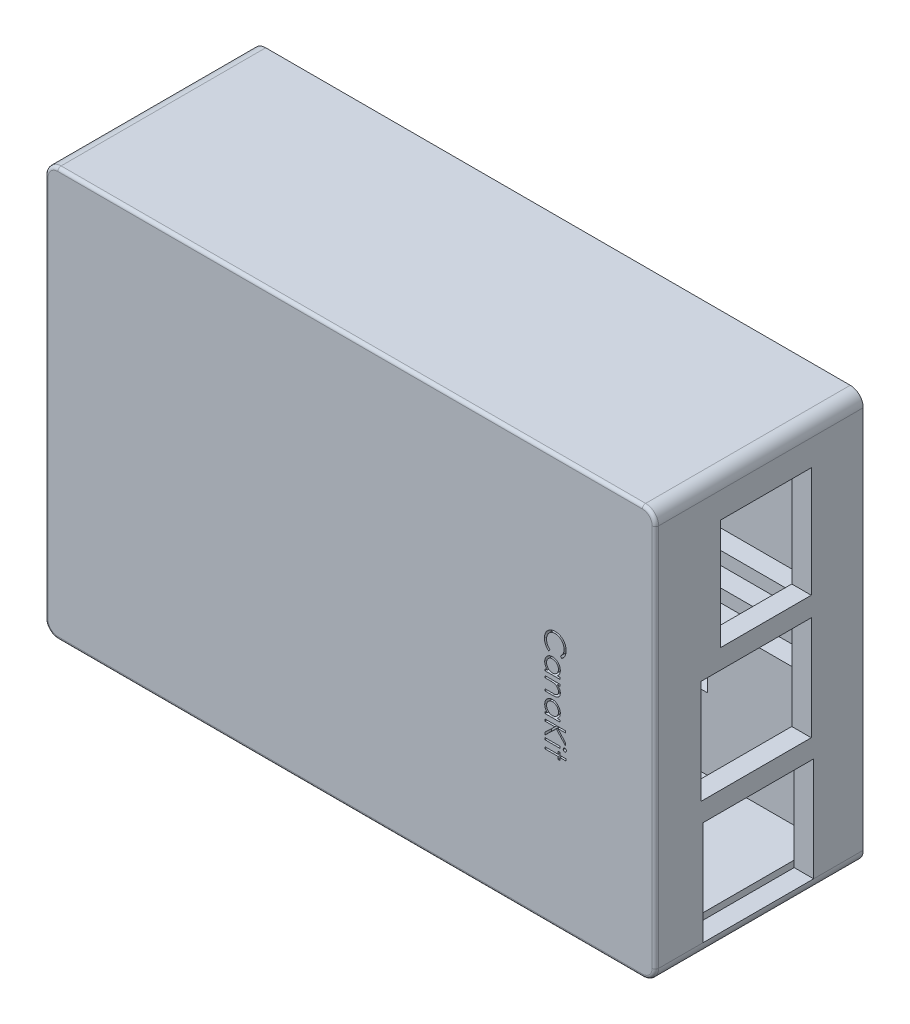
SolidWorks part; units mm, degrees
ref_plane "Front Plane" through (0, 0, 0) normal (0, 0, 1) x (1, 0, 0)
ref_plane "Top Plane" through (0, 0, 0) normal (0, 1, 0) x (1, 0, 0)
ref_plane "Right Plane" through (0, 0, 0) normal (1, 0, 0) x (0, 0, -1)
sketch "Sketch1" plane through (0, 0, 0) normal (0, 0, 1) x (1, 0, 0)
  line L1 (0, 0) -> (94, 0)
  line L2 (0, 0) -> (0, 63)
  line L3 (0, 63) -> (94, 63)
  line L4 (94, 0) -> (94, 63)
  dimension "D1" = 94
  dimension "D2" = 63
extrude "Boss-Extrude1" add sketch "Sketch1" along normal blind 32
shell "Shell1" thickness 3
sketch "Sketch2" plane through (0, 0, 0) normal (-1, 0, 0) x (0, 0, 1)
  line L0 (0, 63) -> (0, 0) construction
  line L1 (8, 40) -> (0, 40)
  line L2 (8, 40) -> (8, 23)
  line L3 (8, 23) -> (0, 23)
  line L4 (0, 40) -> (0, 23)
  line L5 (32, 63) -> (0, 63) construction
  dimension "D1" = 17
  dimension "D2" = 8
  dimension "D3" = 0
  dimension "D4" = 23
extrude "Cut-Extrude1" cut sketch "Sketch2" against normal blind 3
sketch "Sketch3" plane through (94, 0, 0) normal (1, 0, 0) x (0, 0, -1)
  line L0 (-32, 63) -> (0, 63) construction
  line L1 (-22, 40) -> (-8, 40)
  line L2 (-22, 40) -> (-22, 57)
  line L3 (-22, 57) -> (-8, 57)
  line L4 (-8, 40) -> (-8, 57)
  line L5 (0, 0) -> (0, 63) construction
  dimension "D1" = 17
  dimension "D2" = 14
  dimension "D3" = 6
  dimension "D4" = 8
extrude "Cut-Extrude2" cut sketch "Sketch3" against normal blind 3
sketch "Sketch4" plane through (94, 0, 0) normal (1, 0, 0) x (0, 0, -1)
  line L0 (-22, 40) -> (-8, 40) construction
  line L1 (-25, 21) -> (-8, 21)
  line L2 (-25, 21) -> (-25, 37)
  line L3 (-25, 37) -> (-8, 37)
  line L4 (-8, 21) -> (-8, 37)
  line L5 (0, 0) -> (0, 63) construction
  dimension "D1" = 16
  dimension "D2" = 17
  dimension "D3" = 3
  dimension "D4" = 8
extrude "Cut-Extrude4" cut sketch "Sketch4" against normal blind 3
sketch "Sketch5" plane through (94, 0, 0) normal (1, 0, 0) x (0, 0, -1)
  line L0 (-25, 21) -> (-8, 21) construction
  line L1 (-24.6328, 2) -> (-7.6328, 2)
  line L2 (-24.6328, 2) -> (-24.6328, 18)
  line L3 (-24.6328, 18) -> (-7.6328, 18)
  line L4 (-7.6328, 2) -> (-7.6328, 18)
  dimension "D1" = 17
  dimension "D2" = 16
  dimension "D3" = 3
extrude "Cut-Extrude5" cut sketch "Sketch5" against normal blind 3
sketch "Sketch6" plane through (0, 0, 0) normal (0, -1, 0) x (-1, 0, 0)
  line L0 (-94, -32) -> (-94, 0) construction
  line L1 (0, 0) -> (-94, 0) construction
  circle A0 centre (-59, -11) radius 1.75
  dimension "D1" = 3.5
  dimension "D2" = 35
  dimension "D3" = 11
extrude "Cut-Extrude6" cut sketch "Sketch6" against normal blind 3
sketch "Sketch7" plane through (0, 0, 0) normal (0, -1, 0) x (-1, 0, 0)
  line L0 (0, 0) -> (-94, 0) construction
  line L1 (-43, -11) -> (-52, -11)
  line L2 (-43, -11) -> (-43, -8)
  line L3 (-43, -8) -> (-52, -8)
  line L4 (-52, -11) -> (-52, -8)
  line L5 (-28, -11) -> (-37, -11)
  line L6 (-28, -11) -> (-28, -8)
  line L7 (-28, -8) -> (-37, -8)
  line L8 (-37, -11) -> (-37, -8)
  line L9 (-14, -10.5) -> (-22, -10.5)
  line L10 (-14, -10.5) -> (-14, -8)
  line L11 (-14, -8) -> (-22, -8)
  line L12 (-22, -10.5) -> (-22, -8)
  circle A0 centre (-59, -11) radius 1.75 construction
  dimension "D1" = 9
  dimension "D2" = 3
  dimension "D3" = 8
  dimension "D4" = 7
  dimension "D5" = 9
  dimension "D6" = 3
  dimension "D7" = 8
  dimension "D8" = 6
  dimension "D9" = 8
  dimension "D10" = 2.5
  dimension "D11" = 6
  dimension "D12" = 8
extrude "Cut-Extrude7" cut sketch "Sketch7" against normal blind 3
sketch "Sketch9" plane through (0, 0, 32) normal (0, 0, 1) x (1, 0, 0)
  line L0 (77, 60.4844) -> (77, 1.6207) construction
  line L1 (94, 0) -> (94, 63) construction
  text T0 "CanaKit"
  dimension "D1" = 17
extrude "Cut-Extrude8" cut sketch "Sketch9" against normal blind 1
sketch "Sketch11" plane through (0, 0, 0) normal (0, -1, 0) x (1, 0, 0)
  line L0 (-5.7016, 1.5) -> (107.7038, 1.5) construction
  line L1 (0, 0) -> (94, 0) construction
  text T0 "             PWR       HDMI     HDMI    A/V" font "Century Gothic" height in points 10
  dimension "D1" = 1.5
extrude "Cut-Extrude9" cut sketch "Sketch11" against normal blind 1
sketch "Sketch14" plane through (0, 0, 0) normal (0, 0, -1) x (-1, 0, 0)
  line L0 (-94, 63) -> (0, 63) construction
  line L1 (-70, 52) -> (-20, 52)
  line L2 (-70, 52) -> (-70, 49)
  line L3 (-70, 49) -> (-20, 49)
  line L4 (-20, 52) -> (-20, 49)
  line L5 (-94, 0) -> (-94, 63) construction
  line L7 (-73, 47) -> (-23, 47)
  line L8 (-73, 47) -> (-73, 44)
  line L9 (-73, 44) -> (-23, 44)
  line L10 (-23, 47) -> (-23, 44)
  line L11 (-75, 42) -> (-15, 42)
  line L12 (-75, 42) -> (-75, 39)
  line L13 (-75, 39) -> (-15, 39)
  line L14 (-15, 42) -> (-15, 39)
  line L15 (-89, 37) -> (-13, 37)
  line L16 (-89, 37) -> (-89, 34)
  line L17 (-89, 34) -> (-13, 34)
  line L18 (-13, 37) -> (-13, 34)
  line L19 (-86, 32) -> (-10, 32)
  line L20 (-86, 32) -> (-86, 29)
  line L21 (-86, 29) -> (-10, 29)
  line L22 (-10, 32) -> (-10, 29)
  line L23 (-89, 24) -> (-13, 24)
  line L24 (-89, 24) -> (-89, 27)
  line L25 (-89, 27) -> (-13, 27)
  line L26 (-13, 24) -> (-13, 27)
  line L27 (-75, 22) -> (-15, 22)
  line L28 (-75, 22) -> (-75, 19)
  line L29 (-75, 19) -> (-15, 19)
  line L30 (-15, 22) -> (-15, 19)
  line L31 (-73, 17) -> (-23, 17)
  line L32 (-73, 17) -> (-73, 14)
  line L33 (-73, 14) -> (-23, 14)
  line L34 (-23, 17) -> (-23, 14)
  line L35 (-70, 9) -> (-20, 9)
  line L36 (-70, 9) -> (-70, 12)
  line L37 (-70, 12) -> (-20, 12)
  line L38 (-20, 9) -> (-20, 12)
  dimension "D1" = 50
  dimension "D2" = 3
  dimension "D3" = 11
  dimension "D4" = 24
  dimension "D5" = 50
  dimension "D6" = 3
  dimension "D7" = 21
  dimension "D8" = 16
  dimension "D9" = 60
  dimension "D10" = 3
  dimension "D11" = 19
  dimension "D12" = 21
  dimension "D13" = 76
  dimension "D14" = 3
  dimension "D15" = 5
  dimension "D16" = 26
  dimension "D17" = 76
  dimension "D18" = 3
  dimension "D19" = 8
  dimension "D20" = 31
  dimension "D21" = 76
  dimension "D22" = 3
  dimension "D23" = 5
  dimension "D24" = 36
  dimension "D25" = 60
  dimension "D26" = 3
  dimension "D27" = 19
  dimension "D28" = 41
  dimension "D29" = 50
  dimension "D30" = 3
  dimension "D31" = 21
  dimension "D32" = 46
  dimension "D33" = 50
  dimension "D34" = 3
  dimension "D35" = 24
  dimension "D36" = 51
extrude "Cut-Extrude11" cut sketch "Sketch14" against normal blind 10
fillet "Fillet1" radius 2 4 edges at (94, 0, 16) (0, 0, 16) (94, 63, 16) (0, 63, 16)
fillet "Fillet2" radius 0.5 8 edges at (0.5858, 0.5858, 32) (0, 31.5, 32) (0.5858, 62.4142, 32) (47, 63, 32) (93.4142, 62.4142, 32) (94, 31.5, 32) (93.4142, 0.5858, 32) (47, 0, 32)
